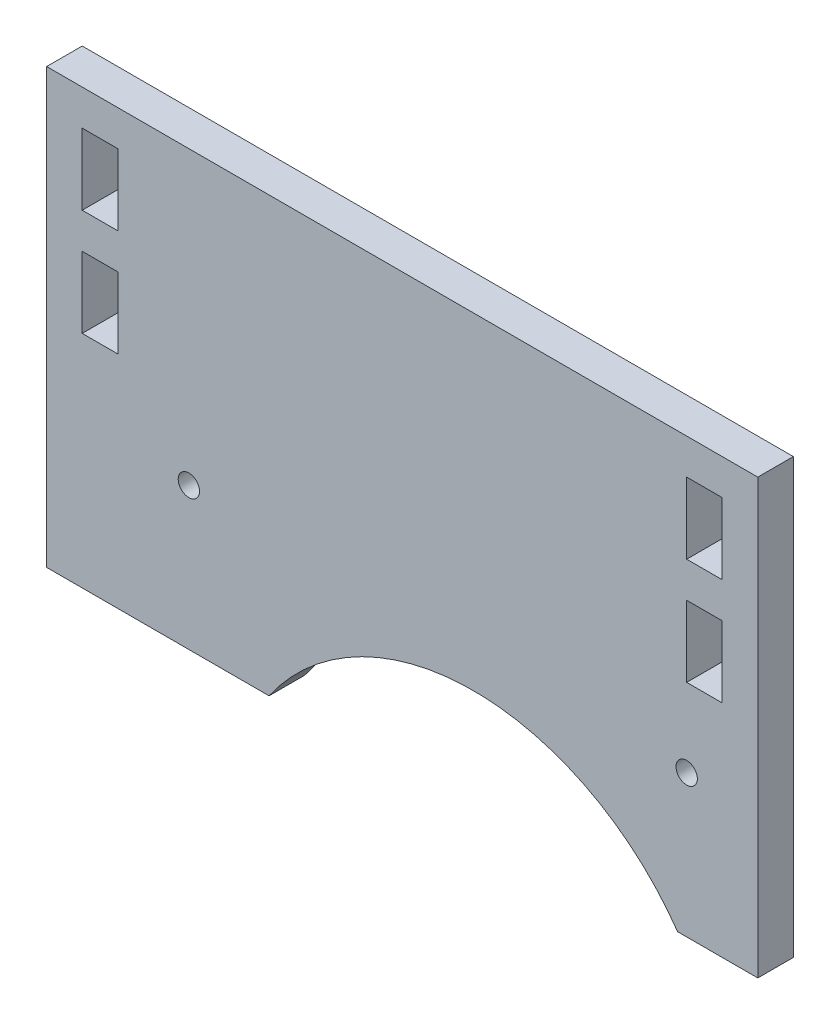
SolidWorks part; units mm, degrees
ref_plane "Plan de face" through (0, 0, 0) normal (0, 0, 1) x (1, 0, 0)
ref_plane "Plan de dessus" through (0, 0, 0) normal (0, 1, 0) x (1, 0, 0)
ref_plane "Plan de droite" through (0, 0, 0) normal (1, 0, 0) x (0, 0, -1)
sketch "Esquisse1" plane through (0, 0, 0) normal (0, 0, 1) x (1, 0, 0)
  line L0 (20, 71) -> (20, 0) construction
  line L1 (0, 0) -> (31.2772, 0)
  line L2 (0, 0) -> (0, 61)
  line L3 (0, 61) -> (100, 61)
  line L4 (100, 0) -> (100, 61)
  line L6 (90, 56) -> (95, 56)
  line L7 (90, 56) -> (90, 46)
  line L8 (90, 46) -> (95, 46)
  line L9 (95, 56) -> (95, 46)
  line L10 (20, 20) -> (90, 20) construction
  line L11 (88.7228, 0) -> (100, 0)
  line L12 (90, 41) -> (95, 41)
  line L13 (90, 41) -> (90, 31)
  line L14 (90, 31) -> (95, 31)
  line L15 (95, 41) -> (95, 31)
  line L16 (5, 56) -> (10, 56)
  line L17 (5, 56) -> (5, 46)
  line L18 (5, 46) -> (10, 46)
  line L19 (10, 56) -> (10, 46)
  line L20 (5, 41) -> (10, 41)
  line L21 (5, 41) -> (5, 31)
  line L22 (5, 31) -> (10, 31)
  line L23 (10, 41) -> (10, 31)
  circle A4 centre (20, 20) radius 1.5
  circle A5 centre (20, 20) radius 1.5 construction
  circle A6 centre (90, 20) radius 1.5
  circle A7 centre (60, -20) radius 35 construction
  arc A8 (31.2772, 0) -> (88.7228, 0) centre (60, -20) cw
  dimension "D6" = 5
  dimension "D8" = 10
  dimension "D9" = 3
  dimension "D10" = 70
  dimension "D13" = 70
  dimension "D16" = 5
  dimension "D2" = 20
  dimension "D3" = 61
  dimension "D4" = 20
  dimension "D5" = 100
  dimension "D7" = 5
  dimension "D11" = 5
  dimension "D12" = 5
  dimension "D14" = 40
  dimension "D15" = 40
extrude "Boss.-Extru.1" add sketch "Esquisse1" along normal blind 5
